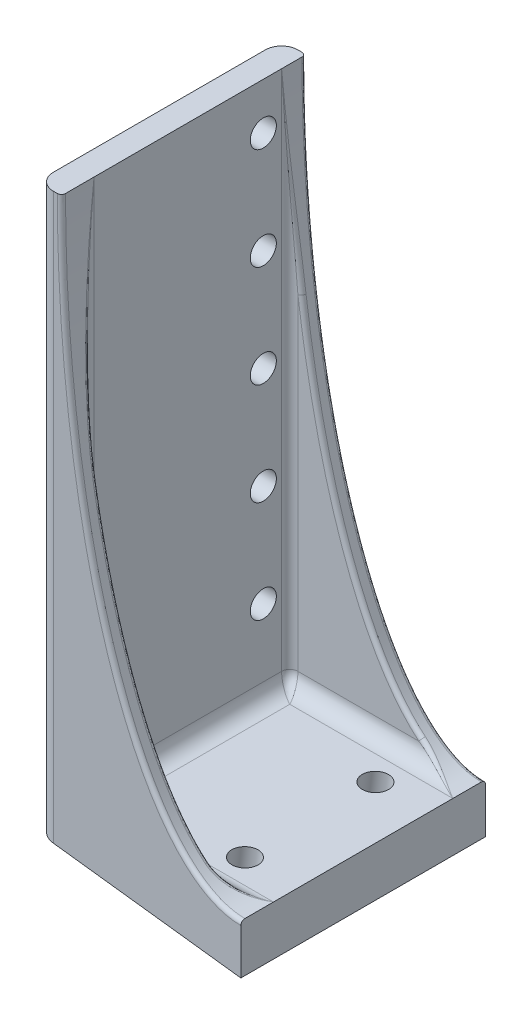
SolidWorks part; units mm, degrees
material "ABS"
ref_plane "Front Plane" through (0, 0, 0) normal (0, 0, 1) x (1, 0, 0)
ref_plane "Top Plane" through (0, 0, 0) normal (0, 1, 0) x (1, 0, 0)
ref_plane "Right Plane" through (0, 0, 0) normal (1, 0, 0) x (0, 0, -1)
sketch "Sketch1" plane through (0, 0, 0) normal (0, 1, 0) x (1, 0, 0)
  line L0 (5.5, 15) -> (5.5, -15)
  line L1 (-12.5, 15) -> (12.5, 15)
  line L2 (-12.5, 15) -> (-12.5, -15)
  line L3 (-12.5, -15) -> (12.5, -15)
  line L4 (12.5, 15) -> (12.5, -15)
  line L5 (0, -15) -> (0, 15) construction
  line L6 (-12.5, 0) -> (12.5, 0) construction
  point P0 (0, 0)
  dimension "D1" = 25
  dimension "D2" = 30
  dimension "D3" = 18
extrude "Boss-Extrude1" add sketch "Sketch1" along normal blind 3 contours L0 L1 L2 L3 | L0 L3 L4 L1 region at (9, 0, 0) region at (-3.5, 0, 0)
sketch "Sketch2" plane through (0, 3, 0) normal (0, 1, 0) x (1, 0, 0)
  line L0 (-9.5, 15) -> (-9.5, -15)
  line L1 (-12.5, 15) -> (12.5, 15)
  line L2 (-12.5, 15) -> (-12.5, -15)
  line L3 (-12.5, -15) -> (12.5, -15)
  line L4 (12.5, 15) -> (12.5, -15)
  line M6 (-12.5, -15) -> (12.5, -15)
  line M8 (12.5, 15) -> (-12.5, 15)
  line M9 (-12.5, 15) -> (-12.5, -15)
  dimension "D1" = 3
extrude "Boss-Extrude2" add sketch "Sketch2" along normal blind 66 contours L0 M8 M9 M6 region at (-11, 3, 0)
sketch "Sketch3" plane through (0, 3, 0) normal (0, 1, 0) x (1, 0, 0)
  line L0 (-9.5, -13) -> (12.5, -13)
  line L1 (-9.5, 15) -> (12.5, 15)
  line L2 (-9.5, 15) -> (-9.5, -15)
  line L3 (-9.5, -15) -> (12.5, -15)
  line L4 (12.5, 15) -> (12.5, -15)
  line L5 (12.5, 0) -> (-9.5, 0) construction
  line L6 (-9.5, 13) -> (12.5, 13)
  line M9 (12.5, 15) -> (-9.5, 15)
  line M10 (-9.5, 15) -> (-9.5, -15)
  line M11 (-9.5, -15) -> (12.5, -15)
  line M12 (12.5, -15) -> (12.5, 15)
  dimension "D1" = 2
sketch "Sketch10" plane through (-12.5, 0, 0) normal (-1, 0, 0) x (0, 0, 1)
  line L0 (-15, 13.3) -> (15, 13.3) construction
  line L1 (-15, 69) -> (15, 69)
  line L2 (-15, 69) -> (-15, 0)
  line L3 (-15, 0) -> (15, 0)
  line L4 (15, 69) -> (15, 0)
  line L5 (-15, 38.3) -> (15, 38.3) construction
  line L6 (-9.755, 38.3) -> (-9.755, 13.3) construction
  line L7 (-12.5, 69) -> (-12.5, 0) construction
  line L8 (-9.755, 38.3) -> (-9.755, 63.3) construction
  circle A0 centre (-9.755, 38.3) radius 1.6
  circle A1 centre (-9.755, 13.3) radius 1.6
  circle A2 centre (-9.755, 63.3) radius 1.6
  circle A3 centre (-9.755, 25.8) radius 1.6
  circle A4 centre (-9.755, 50.8) radius 1.6
  dimension "D5" = 3.2
  dimension "D6" = 3.2
  dimension "D9" = 3.2
  dimension "D11" = 3.2
  dimension "D12" = 3.2
  dimension "D1" = 30
  dimension "D2" = 69
  dimension "D3" = 13.3
  dimension "D4" = 25
  dimension "D7" = 2.745
  dimension "D8" = 2.5
  dimension "D10" = 25
extrude "Cut-Extrude2" cut sketch "Sketch10" against normal blind 40 contours A1 | A0 | A2 | A3 | A4
sketch "Sketch12" plane through (0, 0, -15) normal (0, 0, -1) x (-1, 0, 0)
  line L0 (12.5, 0) -> (-12.5, -3.0696)
  line L1 (-12.5, 3) -> (12.5, 3)
  line L2 (-12.5, 3) -> (-12.5, 0)
  line L3 (-12.5, 0) -> (12.5, 0)
  line L4 (12.5, 3) -> (12.5, 0)
  line L5 (-12.5, -3.0696) -> (-12.5, 0)
  line M6 (-12.5, 0) -> (12.5, 0)
  dimension "D1" = 7
extrude "Boss-Extrude3" add sketch "Sketch12" against normal up to surface (30 mm away) contours L5 L0 M6 region at (4.1667, -1.0232, -15) up to face at (-3.1667, 24, 15)
sketch "Sketch13" plane through (-0.1857, -1.512, 0) normal (-0.1219, -0.9925, 0) x (0.9925, -0.1219, 0)
  line L0 (12.7809, 0) -> (-12.4068, 0) construction
  line L1 (12.7809, -15) -> (-12.4068, -15)
  line L2 (12.7809, -15) -> (12.7809, 15)
  line L3 (12.7809, 15) -> (-12.4068, 15)
  line L4 (-12.4068, -15) -> (-12.4068, 15)
  line L5 (12.7809, 8) -> (-12.4068, 8) construction
  line L6 (5.5932, 15) -> (5.5932, 0) construction
  circle A0 centre (5.5932, 8) radius 1.6
  circle A1 centre (5.5932, -8) radius 1.6
  point P14 (0, 0)
  point P15 (0, 0)
  dimension "D3" = 3.2
  dimension "D1" = 8
  dimension "D2" = 18
extrude "Cut-Extrude3" cut sketch "Sketch13" against normal blind 10 contours A1 | A0
extrude "Boss-Extrude4" add sketch "Sketch3" along normal blind 66 contours L0 M10 M11 M12 | L6 L4 M10 M9 region at (1.5, 3, 14) region at (1.5, 3, -14)
sketch "Sketch16" plane through (0, 0, -13) normal (0, 0, 1) x (1, 0, 0)
  ellipse E0 centre (12.5, 69) end of major axis (12.5, 3) minor radius 22
extrude "Cut-Extrude4" cut sketch "Sketch16" against normal through all both and the other way through all
fillet "Fillet1" radius 2 4 edges at (-9.5, 36, 13) (1.5, 3, -13) (1.5, 3, 13) (-9.5, 3, 0)
fillet "Fillet2" radius 1 2 edges at (-8.9142, 3.5858, -12.4142) (-9.5, 37, -13)
fillet "Fillet3" radius 0.5 8 edges at (8.7039, 3.9899, 12.7262) (-8.0539, 45.4663, 12.9218) (8.7039, 3.9899, -12.7262) (-8.6958, 51.3181, -12.9806) (-1.5708, 18.2642, 13) (-3.0563, 22.331, 15) (-2.6159, 21.0459, -13) (-3.0563, 22.331, -15)
fillet "Fillet7" radius 2 2 edges at (-12.5, 34.5, -15) (-12.5, 34.5, 15)
